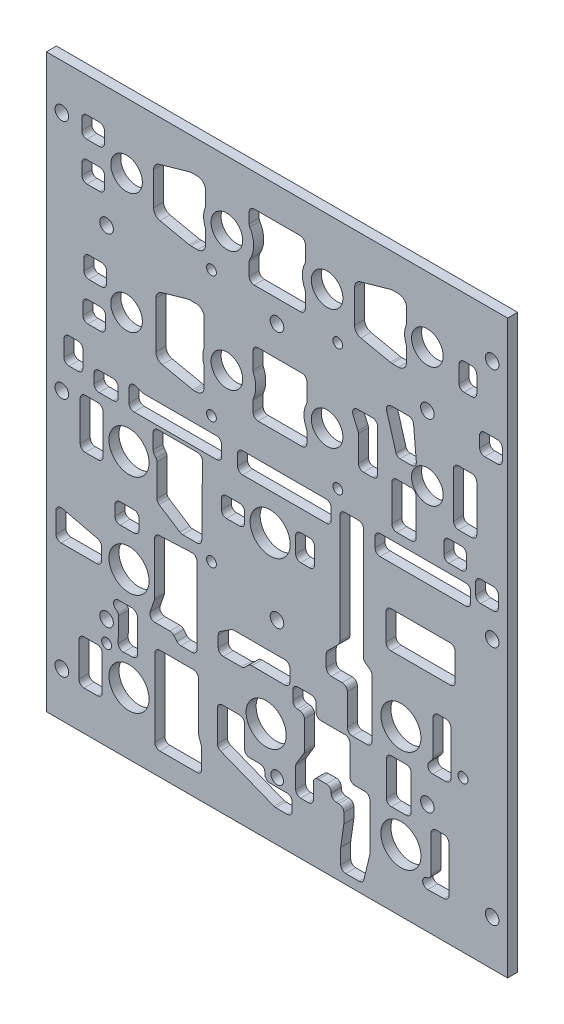
SolidWorks part; units mm, degrees
ref_plane "Front Plane" through (0, 0, 0) normal (0, 0, 1) x (1, 0, 0)
ref_plane "Top Plane" through (0, 0, 0) normal (0, 1, 0) x (1, 0, 0)
ref_plane "Right Plane" through (0, 0, 0) normal (1, 0, 0) x (0, 0, -1)
sketch "Sketch1" plane through (0, 0, 0) normal (0, 0, 1) x (1, 0, 0)
  line L4 (0, 180.975) -> (-146.05, 180.975)
  line L5 (-146.05, 180.975) -> (-146.05, 0)
  line L6 (-146.05, 0) -> (0, 0)
  line L7 (0, 0) -> (0, 180.975)
  line L8 (0, 180.975) -> (-146.05, 180.975)
  line L9 (-146.05, 180.975) -> (-146.05, 0)
  line L10 (-146.05, 0) -> (0, 0)
  line L11 (0, 0) -> (0, 180.975)
  dimension "D1" = 0
extrude "Boss-Extrude1" add sketch "Sketch1" against normal blind 3.175
hole_wizard "#6 Clearance Hole1" positions "Sketch3" profile "Sketch2" hole size "#6" standard "ANSI Inch" end condition through all
sketch "Sketch3" plane through (0, 0, -3.175) normal (0, 0, -1) x (-1, 0, 0)
  point P0 (25.4, 142.875)
  point P7 (73.025, 142.875)
  point P10 (127, 142.875)
  point P13 (25.4, 34.925)
  point P16 (73.025, 61.647)
  point P19 (127, 34.925)
  point P22 (4.8895, 14.2875)
  point P25 (141.1605, 14.2875)
  point P28 (4.8895, 90.4875)
  point P31 (141.1605, 90.4875)
  point P34 (141.1605, 166.6875)
  point P37 (4.8895, 166.6875)
sketch "Sketch2" plane through (-25.4, 142.875, -3.175) normal (1, 0, 0) x (0, 1, 0)
  line L0 (0, 0) -> (0, 3.175)
  line L1 (0, 3.175) -> (2.1526, 3.175)
  line L2 (2.1526, 3.175) -> (2.1526, 0)
  line L5 (2.1526, 0) -> (0, 0)
  line L11 (0, -6.35) -> (0, 107.95) construction
  dimension "Thru Hole Dia." = 4.3053
  dimension "Thru Hole Depth" = 3.175
hole_wizard "Ø10.0mm Dowel Hole1" positions "Sketch5" profile "Sketch4" hole size "Ø10.0" standard "ANSI Metric" end condition through all
sketch "Sketch5" plane through (0, 0, -3.175) normal (0, 0, -1) x (-1, 0, 0)
  point P0 (25.4, 160.3248)
  point P3 (57.15, 160.3248)
  point P6 (88.9, 160.3248)
  point P9 (120.65, 160.3248)
  point P12 (25.4, 122.2248)
  point P15 (57.15, 122.2248)
  point P18 (88.9, 122.2248)
  point P21 (120.65, 122.2248)
sketch "Sketch4" plane through (-25.4, 160.3248, -3.175) normal (1, 0, 0) x (0, 1, 0)
  line L0 (0, 0) -> (0, 3.175)
  line L1 (0, 3.175) -> (5, 3.175)
  line L2 (5, 3.175) -> (5, 0)
  line L5 (5, 0) -> (0, 0)
  line L11 (0, -6.35) -> (0, 107.95) construction
  dimension "Thru Hole Dia." = 10
  dimension "Thru Hole Depth" = 3.175
hole_wizard "1/2 (0.5) Diameter Hole1" positions "Sketch7" profile "Sketch6" hole size "1/2" standard "ANSI Inch" end condition through all
sketch "Sketch7" plane through (0, 0, -3.175) normal (0, 0, -1) x (-1, 0, 0)
  point P0 (75.184, 84.455)
  point P3 (119.888, 84.455)
  point P6 (119.888, 52.07)
  point P9 (33.782, 52.07)
  point P12 (33.782, 19.685)
  point P15 (119.888, 19.685)
  point P18 (76.454, 31.496)
sketch "Sketch6" plane through (-75.184, 84.455, -3.175) normal (1, 0, 0) x (0, 1, 0)
  line L0 (0, 0) -> (0, 3.175)
  line L1 (0, 3.175) -> (6.35, 3.175)
  line L2 (6.35, 3.175) -> (6.35, 0)
  line L5 (6.35, 0) -> (0, 0)
  line L11 (0, -6.35) -> (0, 107.95) construction
  dimension "Thru Hole Dia." = 12.7
  dimension "Thru Hole Depth" = 3.175
hole_wizard "5/32 (0.15625) Diameter Hole1" positions "Sketch9" profile "Sketch8" hole size "5/32" standard "ANSI Inch" end condition through all
sketch "Sketch9" plane through (0, 0, -3.175) normal (0, 0, -1) x (-1, 0, 0)
  point P0 (72.9632, 18.4682)
sketch "Sketch8" plane through (-72.9632, 18.4682, -3.175) normal (1, 0, 0) x (0, 1, 0)
  line L0 (0, 0) -> (0, 3.175)
  line L1 (0, 3.175) -> (1.9844, 3.175)
  line L2 (1.9844, 3.175) -> (1.9844, 0)
  line L5 (1.9844, 0) -> (0, 0)
  line L11 (0, -6.35) -> (0, 107.95) construction
  dimension "Thru Hole Dia." = 3.9688
  dimension "Thru Hole Depth" = 3.175
sketch "Sketch14" plane through (0, 0, -3.175) normal (0, 0, -1) x (-1, 0, 0)
  line L0 (9.7672, 160.6329) -> (9.7672, 155.3272)
  line L1 (11.3547, 153.7397) -> (13.8015, 153.7397)
  line L2 (15.389, 155.3272) -> (15.389, 160.6329)
  line L3 (13.8015, 162.2204) -> (11.3547, 162.2204)
  line L4 (34.5586, 170.4142) -> (36.4003, 170.4142)
  line L5 (37.0961, 170.317) -> (46.6191, 167.6046)
  line L6 (48.4633, 165.1617) -> (48.4633, 154.7406)
  line L7 (46.4489, 152.2556) -> (37.1235, 150.2836)
  line L8 (36.598, 150.2286) -> (34.5586, 150.2286)
  line L9 (32.0186, 152.7686) -> (32.0186, 156.9396)
  line L10 (32.0186, 163.6743) -> (32.0186, 167.8742)
  line L11 (98.2115, 170.808) -> (100.0532, 170.808)
  line L12 (100.749, 170.7109) -> (110.272, 167.9984)
  line L13 (112.1162, 165.5556) -> (112.1162, 155.1345)
  line L14 (110.1017, 152.6494) -> (100.7763, 150.6774)
  line L15 (100.2508, 150.6225) -> (98.2115, 150.6225)
  line L16 (95.6715, 153.1625) -> (95.6715, 157.3335)
  line L17 (95.6715, 164.0681) -> (95.6715, 168.268)
  line L18 (81.8281, 169.1678) -> (81.8281, 165.8804)
  line L19 (80.2406, 149.9091) -> (65.6522, 149.9091)
  line L20 (64.0647, 151.4966) -> (64.0647, 156.2088)
  line L21 (65.6522, 170.7553) -> (80.2406, 170.7553)
  line L22 (81.8281, 155.5212) -> (81.8281, 151.4966)
  line L23 (64.0647, 164.4051) -> (64.0647, 169.1678)
  line L24 (129.2512, 170.0673) -> (133.2539, 170.0673)
  line L25 (134.8414, 168.4798) -> (134.8414, 164.9772)
  line L26 (133.2539, 163.3897) -> (129.2512, 163.3897)
  line L27 (127.6637, 164.9772) -> (127.6637, 168.4798)
  line L28 (129.2048, 157.7974) -> (133.2075, 157.7974)
  line L29 (134.795, 156.2099) -> (134.795, 152.7072)
  line L30 (133.2075, 151.1197) -> (129.2048, 151.1197)
  line L31 (127.6173, 152.7072) -> (127.6173, 156.2099)
  line L38 (9.7672, 131.1028) -> (9.7672, 116.698)
  line L39 (3.2616, 146.0268) -> (7.2643, 146.0268)
  line L40 (8.8518, 144.4393) -> (8.8518, 140.9366)
  line L41 (7.2643, 139.3491) -> (3.2616, 139.3491)
  line L42 (1.6741, 140.9366) -> (1.6741, 144.4393)
  line L43 (31.3598, 138.4891) -> (36.773, 138.4891)
  line L44 (38.2969, 136.4568) -> (35.3321, 126.2979)
  line L45 (34.083, 125.3612) -> (30.4776, 125.3612)
  line L46 (28.8963, 127.0889) -> (29.7785, 137.0417)
  line L47 (11.3547, 115.1105) -> (15.5328, 115.1105)
  line L48 (17.1203, 116.698) -> (17.1203, 131.1028)
  line L49 (15.5328, 132.6903) -> (11.3547, 132.6903)
  line L50 (48.956, 130.0101) -> (47.363, 126.3421)
  line L51 (47.2316, 125.7097) -> (47.2316, 117.4914)
  line L52 (45.6441, 115.9039) -> (42.7293, 115.9039)
  line L53 (41.1418, 117.4914) -> (41.1418, 130.6425)
  line L54 (42.7293, 132.23) -> (47.4999, 132.23)
  line L55 (80.6037, 131.7198) -> (80.6037, 126.3538)
  line L56 (79.0162, 113.2168) -> (65.1559, 113.2168)
  line L57 (63.5684, 114.8043) -> (63.5684, 118.2429)
  line L58 (65.1559, 133.3073) -> (79.0162, 133.3073)
  line L59 (80.6037, 118.0601) -> (80.6037, 114.8043)
  line L60 (63.5684, 126.171) -> (63.5684, 131.7198)
  line L61 (98.5982, 135.6202) -> (100.6455, 135.6202)
  line L62 (101.3413, 135.523) -> (109.5302, 133.1906)
  line L63 (111.3744, 130.7477) -> (111.3744, 116.0074)
  line L64 (109.3599, 113.5224) -> (99.6649, 111.4722)
  line L65 (99.1394, 111.4172) -> (98.5982, 111.4172)
  line L66 (96.0582, 113.9572) -> (96.0582, 119.3928)
  line L67 (96.0582, 125.1954) -> (96.0582, 133.0802)
  line L68 (128.5836, 131.9356) -> (132.5863, 131.9356)
  line L69 (134.1738, 130.3481) -> (134.1738, 126.8454)
  line L70 (132.5863, 125.2579) -> (128.5836, 125.2579)
  line L71 (126.9961, 126.8454) -> (126.9961, 130.3481)
  line L72 (128.8955, 119.5754) -> (132.8982, 119.5754)
  line L73 (134.4857, 117.9879) -> (134.4857, 114.4852)
  line L74 (132.8982, 112.8977) -> (128.8955, 112.8977)
  line L75 (127.308, 114.4852) -> (127.308, 117.9879)
  line L80 (134.4857, 99.9647) -> (134.4857, 105.0965)
  line L81 (136.0732, 106.684) -> (138.8818, 106.684)
  line L82 (140.4693, 105.0965) -> (140.4693, 99.9647)
  line L83 (138.8818, 98.3772) -> (136.0732, 98.3772)
  line L84 (4.5173, 105.1016) -> (8.52, 105.1016)
  line L85 (10.1075, 103.5141) -> (10.1075, 100.0114)
  line L86 (8.52, 98.4239) -> (4.5173, 98.4239)
  line L87 (2.9298, 100.0114) -> (2.9298, 103.5141)
  line L88 (14.5909, 111.1372) -> (18.5937, 111.1372)
  line L89 (20.1812, 109.5497) -> (20.1812, 106.0471)
  line L90 (18.5937, 104.4596) -> (14.5909, 104.4596)
  line L91 (13.0034, 106.0471) -> (13.0034, 109.5497)
  line L92 (30.5353, 119.2048) -> (35.0928, 119.2048)
  line L93 (36.6803, 117.6173) -> (36.6803, 106.232)
  line L94 (35.0928, 104.6445) -> (30.5353, 104.6445)
  line L95 (28.9478, 106.232) -> (28.9478, 117.6173)
  line L96 (45.6441, 65.1535) -> (45.6441, 100.3349)
  line L97 (47.2316, 101.9224) -> (51.5303, 101.9224)
  line L98 (53.1178, 100.3349) -> (53.1178, 65.7835)
  line L100 (42.9626, 43.3689) -> (42.9626, 61.5953)
  line L101 (43.6218, 62.8831) -> (44.9849, 63.8657)
  line L102 (53.5828, 64.661) -> (56.969, 61.2747)
  line L103 (57.434, 60.1522) -> (57.434, 56.3979)
  line L104 (55.8465, 54.8104) -> (52.3434, 54.8104)
  line L105 (50.7559, 53.2229) -> (50.7559, 43.3689)
  line L106 (49.1684, 41.7814) -> (44.5501, 41.7814)
  line L107 (67.1117, 82.7287) -> (67.1117, 87.7639)
  line L108 (65.5242, 89.3514) -> (62.7089, 89.3514)
  line L109 (61.1214, 87.7639) -> (61.1214, 82.7287)
  line L110 (62.7089, 81.1412) -> (65.5242, 81.1412)
  line L111 (17.9628, 45.6888) -> (17.9628, 59.6872)
  line L112 (19.5503, 61.2747) -> (21.9934, 61.2747)
  line L113 (23.5809, 59.6872) -> (23.5809, 48.8911)
  line L114 (23.9452, 47.8792) -> (24.9202, 46.7007)
  line L115 (23.697, 44.1013) -> (19.5503, 44.1013)
  line L116 (25.4886, 14.7678) -> (25.6589, 14.7487)
  line L117 (24.2487, 16.3262) -> (24.2487, 27.6802)
  line L118 (22.6612, 29.2677) -> (20.1812, 29.2677)
  line L119 (18.5937, 27.6802) -> (18.5937, 13.2755)
  line L120 (20.1548, 11.6882) -> (25.2848, 11.603)
  line L121 (32.1228, 42.5427) -> (36.8165, 42.5427)
  line L122 (38.404, 40.9552) -> (38.404, 30.1729)
  line L123 (36.8165, 28.5854) -> (32.1228, 28.5854)
  line L124 (30.5353, 30.1729) -> (30.5353, 40.9552)
  line L131 (43.6218, 25.2523) -> (43.6218, 12.2392)
  line L132 (43.6651, 11.8711) -> (43.6953, 11.7446)
  line L133 (43.6953, 11.7446) -> (45.484, 4.241)
  line L134 (47.0282, 3.0216) -> (51.2631, 3.0216)
  line L135 (52.8506, 4.6091) -> (52.8506, 9.2853)
  line L136 (52.8343, 9.5123) -> (51.8747, 16.1533)
  line L137 (51.8584, 16.3803) -> (51.8584, 19.4808)
  line L138 (53.4459, 21.0683) -> (54.259, 21.0683)
  line L139 (55.8465, 22.6558) -> (55.8465, 22.9529)
  line L140 (57.434, 24.5404) -> (59.9239, 24.5404)
  line L142 (65.7683, 40.3849) -> (66.5835, 40.4562)
  line L143 (68.0326, 42.0377) -> (68.0326, 44.998)
  line L144 (66.4451, 46.5855) -> (62.2379, 46.5855)
  line L145 (60.6504, 44.998) -> (60.6504, 42.5992)
  line L146 (59.0629, 41.0117) -> (51.4951, 41.0117)
  line L147 (49.9076, 39.4242) -> (49.9076, 30.1729)
  line L148 (48.3201, 28.5854) -> (45.2093, 28.5854)
  line L149 (43.6218, 26.9979) -> (43.6218, 25.2523)
  line L150 (68.9553, 46.6546) -> (68.9553, 50.4494)
  line L151 (70.5428, 52.0369) -> (86.6326, 52.0369)
  line L152 (87.4873, 51.7871) -> (90.8944, 49.6101)
  line L153 (91.6271, 48.2724) -> (91.6271, 44.761)
  line L154 (90.0396, 43.1735) -> (84.3014, 43.1735)
  line L155 (83.1789, 43.6384) -> (82.1297, 44.6876)
  line L156 (80.9942, 45.1525) -> (70.5558, 45.0672)
  line L157 (67.1117, 24.5868) -> (67.1117, 18.1303)
  line L158 (65.5242, 16.5428) -> (63.0989, 16.5428)
  line L163 (61.5114, 18.1303) -> (61.5114, 22.9529)
  line L165 (66.8832, 25.4074) -> (64.5524, 29.2677)
  line L166 (64.3238, 30.0883) -> (64.3238, 38.9242)
  line L167 (91.9128, 18.299) -> (91.9128, 28.1134)
  line L168 (90.3253, 29.7009) -> (84.8895, 29.7009)
  line L169 (83.302, 28.1134) -> (83.302, 21.1236)
  line L170 (81.7145, 19.5361) -> (78.4438, 19.5361)
  line L171 (76.8563, 17.9486) -> (76.8563, 17.3807)
  line L172 (75.2688, 15.7932) -> (69.8184, 15.7932)
  line L173 (68.2309, 14.2057) -> (68.2309, 11.594)
  line L174 (69.8184, 10.0065) -> (73.3881, 10.0065)
  line L175 (73.9724, 10.1179) -> (90.9097, 16.8229)
  line L176 (84.8489, 87.7639) -> (89.0654, 87.7639)
  line L177 (90.6529, 86.1764) -> (90.6529, 83.1046)
  line L178 (89.0654, 81.5171) -> (84.8489, 81.5171)
  line L179 (83.2614, 83.1046) -> (83.2614, 86.1764)
  line L180 (129.7198, 92.9203) -> (133.7466, 92.9203)
  line L181 (135.3341, 91.3328) -> (135.3341, 78.857)
  line L182 (133.7466, 77.2695) -> (129.7198, 77.2695)
  line L183 (128.1323, 78.857) -> (128.1323, 91.3328)
  line L184 (143.02, 56.7173) -> (143.02, 50.184)
  line L185 (141.4325, 48.5965) -> (130.1711, 48.5965)
  line L186 (128.5836, 50.184) -> (128.5836, 54.036)
  line L187 (129.8034, 55.5803) -> (141.0648, 58.2616)
  line L188 (135.7336, 24.8954) -> (135.7336, 14.0589)
  line L189 (134.1461, 12.4714) -> (129.9507, 12.4714)
  line L190 (128.3632, 14.0589) -> (128.3632, 24.8954)
  line L191 (129.9507, 26.4829) -> (134.1461, 26.4829)
  line L192 (98.4374, 70.1232) -> (102.927, 70.1232)
  line L193 (103.7933, 70.3805) -> (110.3296, 74.6375)
  line L194 (111.0507, 75.9677) -> (111.0507, 86.0205)
  line L195 (111.3413, 86.936) -> (111.9636, 87.8177)
  line L196 (112.2542, 88.7332) -> (112.2542, 93.4348)
  line L197 (110.6667, 95.0223) -> (98.2147, 95.0223)
  line L198 (96.6273, 93.4186) -> (96.85, 71.6944)
  line L199 (13.2867, 101.7189) -> (40.3927, 101.7189)
  line L200 (41.9802, 100.1314) -> (41.9802, 96.9635)
  line L201 (40.3927, 95.376) -> (13.2867, 95.376)
  line L202 (11.6992, 96.9635) -> (11.6992, 100.1314)
  line L203 (83.9216, 102.6251) -> (57.434, 102.6251)
  line L204 (55.8465, 101.0376) -> (55.8465, 97.6017)
  line L205 (57.434, 96.0142) -> (83.9216, 96.0142)
  line L206 (85.5091, 97.6017) -> (85.5091, 101.0376)
  line L207 (92.1689, 102.6251) -> (115.232, 102.6251)
  line L208 (115.789, 102.726) -> (117.7111, 103.4462)
  line L209 (119.8556, 101.9596) -> (119.8556, 97.6777)
  line L210 (118.2681, 96.0902) -> (92.1689, 96.0902)
  line L211 (90.5814, 97.6777) -> (90.5814, 101.0376)
  line L212 (124.9027, 101.9596) -> (129.3791, 101.9596)
  line L213 (130.9666, 100.3721) -> (130.9666, 97.4731)
  line L214 (129.3791, 95.8856) -> (124.9027, 95.8856)
  line L215 (123.3152, 97.4731) -> (123.3152, 100.3721)
  line L216 (118.2868, 62.8831) -> (122.7428, 62.8831)
  line L217 (124.3303, 64.4706) -> (124.3303, 67.6675)
  line L218 (122.7428, 69.255) -> (118.2868, 69.255)
  line L219 (116.6993, 67.6675) -> (116.6993, 64.4706)
  line L220 (99.9975, 66.6672) -> (110.2768, 66.2149)
  line L221 (111.7946, 64.6289) -> (111.7946, 48.1514)
  line L222 (111.8816, 47.6331) -> (113.2086, 43.7913)
  line L223 (111.7081, 41.6855) -> (106.9185, 41.6855)
  line L224 (105.6937, 41.108) -> (104.7376, 39.9485)
  line L225 (103.5128, 39.371) -> (99.9277, 39.371)
  line L226 (98.3402, 40.9585) -> (98.3402, 65.0812)
  line L227 (123.3155, 30.1394) -> (123.1999, 37.6519)
  line L231 (117.1597, 40.098) -> (117.1597, 30.2424)
  line L232 (118.6794, 28.6564) -> (121.6604, 28.5289)
  line L235 (119.0974, 42.0356) -> (123.1757, 42.0356)
  line L236 (124.1569, 39.2002) -> (123.806, 38.9242)
  line L237 (18.1752, 71.248) -> (36.9199, 71.248)
  line L238 (99.477, 34.8237) -> (110.1206, 34.8237)
  line L239 (111.7081, 33.2362) -> (111.7081, 8.7739)
  line L240 (110.1206, 7.1864) -> (98.4375, 7.1864)
  line L241 (96.85, 8.7739) -> (96.85, 14.4973)
  line L242 (96.9277, 14.9877) -> (97.8118, 17.7095)
  line L243 (97.8895, 18.1999) -> (97.8895, 33.2362)
  line L244 (38.5074, 72.8355) -> (38.5074, 81.2425)
  line L245 (36.9199, 82.83) -> (18.1752, 82.83)
  line L246 (16.5877, 81.2425) -> (16.5877, 72.8355)
  line L247 (93.7721, 147.2947) -> (53.7721, 147.2947) construction
  line L248 (93.7721, 147.2947) -> (93.7721, 107.2947) construction
  line L249 (93.7721, 107.2947) -> (53.7721, 107.2947) construction
  line L250 (53.7721, 147.2947) -> (53.7721, 107.2947) construction
  line L251 (93.7721, 107.2947) -> (93.7721, 67.2947) construction
  arc A0 (13.8015, 153.7397) -> (15.389, 155.3272) centre (13.8015, 155.3272) ccw
  arc A1 (9.7672, 160.6329) -> (11.3547, 162.2204) centre (11.3547, 160.6329) cw
  arc A2 (15.389, 160.6329) -> (13.8015, 162.2204) centre (13.8015, 160.6329) ccw
  arc A3 (9.7672, 155.3272) -> (11.3547, 153.7397) centre (11.3547, 155.3272) ccw
  arc A4 (34.5586, 150.2286) -> (32.0186, 152.7686) centre (34.5586, 152.7686) cw
  arc A5 (37.1235, 150.2836) -> (36.598, 150.2286) centre (36.598, 152.7686) cw
  arc A6 (48.4633, 154.7406) -> (46.4489, 152.2556) centre (45.9233, 154.7406) cw
  arc A7 (46.6191, 167.6046) -> (48.4633, 165.1617) centre (45.9233, 165.1617) cw
  arc A8 (36.4003, 170.4142) -> (37.0961, 170.317) centre (36.4003, 167.8742) cw
  arc A9 (34.5586, 170.4142) -> (32.0186, 167.8742) centre (34.5586, 167.8742) ccw
  arc A10 (32.1741, 157.8147) -> (32.1741, 162.7992) centre (25.3826, 160.3069) ccw
  arc A11 (32.1741, 162.7992) -> (32.0186, 163.6743) centre (34.5586, 163.6743) cw
  arc A12 (32.1741, 157.8147) -> (32.0186, 156.9396) centre (34.5586, 156.9396) ccw
  arc A13 (98.2115, 150.6225) -> (95.6715, 153.1625) centre (98.2115, 153.1625) cw
  arc A14 (100.7763, 150.6774) -> (100.2508, 150.6225) centre (100.2508, 153.1625) cw
  arc A15 (112.1162, 155.1345) -> (110.1017, 152.6494) centre (109.5762, 155.1345) cw
  arc A16 (110.272, 167.9984) -> (112.1162, 165.5556) centre (109.5762, 165.5556) cw
  arc A17 (100.0532, 170.808) -> (100.749, 170.7109) centre (100.0532, 168.268) cw
  arc A18 (98.2115, 170.808) -> (95.6715, 168.268) centre (98.2115, 168.268) ccw
  arc A19 (95.8269, 158.2085) -> (95.8269, 163.1931) centre (89.0355, 160.7008) ccw
  arc A20 (95.8269, 163.1931) -> (95.6715, 164.0681) centre (98.2115, 164.0681) cw
  arc A21 (95.8269, 158.2085) -> (95.6715, 157.3335) centre (98.2115, 157.3335) ccw
  arc A22 (64.2216, 156.8969) -> (64.2216, 163.7169) centre (57.1326, 160.3069) ccw
  arc A23 (81.6085, 165.0748) -> (81.6085, 156.3268) centre (89.0355, 160.7008) ccw
  arc A24 (64.2216, 163.7169) -> (64.0647, 164.4051) centre (65.6522, 164.4051) cw
  arc A25 (64.2216, 156.8969) -> (64.0647, 156.2088) centre (65.6522, 156.2088) ccw
  arc A26 (81.6085, 156.3268) -> (81.8281, 155.5212) centre (80.2406, 155.5212) cw
  arc A27 (81.6085, 165.0748) -> (81.8281, 165.8804) centre (80.2406, 165.8804) ccw
  arc A28 (81.8281, 169.1678) -> (80.2406, 170.7553) centre (80.2406, 169.1678) ccw
  arc A29 (64.0647, 169.1678) -> (65.6522, 170.7553) centre (65.6522, 169.1678) cw
  arc A30 (65.6522, 149.9091) -> (64.0647, 151.4966) centre (65.6522, 151.4966) cw
  arc A31 (81.8281, 151.4966) -> (80.2406, 149.9091) centre (80.2406, 151.4966) cw
  arc A32 (129.2512, 170.0673) -> (127.6637, 168.4798) centre (129.2512, 168.4798) ccw
  arc A33 (129.2512, 163.3897) -> (127.6637, 164.9772) centre (129.2512, 164.9772) cw
  arc A34 (134.8414, 164.9772) -> (133.2539, 163.3897) centre (133.2539, 164.9772) cw
  arc A35 (133.2539, 170.0673) -> (134.8414, 168.4798) centre (133.2539, 168.4798) cw
  arc A36 (129.2048, 157.7974) -> (127.6173, 156.2099) centre (129.2048, 156.2099) ccw
  arc A37 (129.2048, 151.1197) -> (127.6173, 152.7072) centre (129.2048, 152.7072) cw
  arc A38 (134.795, 152.7072) -> (133.2075, 151.1197) centre (133.2075, 152.7072) cw
  arc A39 (133.2075, 157.7974) -> (134.795, 156.2099) centre (133.2075, 156.2099) cw
  arc A50 (29.7785, 137.0417) -> (31.3598, 138.4891) centre (31.3598, 136.9016) cw
  arc A51 (3.2616, 146.0268) -> (1.6741, 144.4393) centre (3.2616, 144.4393) ccw
  arc A52 (3.2616, 139.3491) -> (1.6741, 140.9366) centre (3.2616, 140.9366) cw
  arc A53 (8.8518, 140.9366) -> (7.2643, 139.3491) centre (7.2643, 140.9366) cw
  arc A54 (7.2643, 146.0268) -> (8.8518, 144.4393) centre (7.2643, 144.4393) cw
  arc A55 (128.5836, 131.9356) -> (126.9961, 130.3481) centre (128.5836, 130.3481) ccw
  arc A56 (36.773, 138.4891) -> (38.2969, 136.4568) centre (36.773, 136.9016) cw
  arc A57 (30.4776, 125.3612) -> (28.8963, 127.0889) centre (30.4776, 126.9487) cw
  arc A58 (35.3321, 126.2979) -> (34.083, 125.3612) centre (34.083, 126.6624) cw
  arc A60 (9.7672, 116.698) -> (11.3547, 115.1105) centre (11.3547, 116.698) ccw
  arc A61 (15.5328, 115.1105) -> (17.1203, 116.698) centre (15.5328, 116.698) ccw
  arc A62 (17.1203, 131.1028) -> (15.5328, 132.6903) centre (15.5328, 131.1028) ccw
  arc A63 (9.7672, 131.1028) -> (11.3547, 132.6903) centre (11.3547, 131.1028) cw
  arc A64 (42.7293, 115.9039) -> (41.1418, 117.4914) centre (42.7293, 117.4914) cw
  arc A65 (47.2316, 117.4914) -> (45.6441, 115.9039) centre (45.6441, 117.4914) cw
  arc A66 (47.363, 126.3421) -> (47.2316, 125.7097) centre (48.8191, 125.7097) ccw
  arc A67 (41.1418, 130.6425) -> (42.7293, 132.23) centre (42.7293, 130.6425) cw
  arc A68 (48.956, 130.0101) -> (47.4999, 132.23) centre (47.4999, 130.6425) ccw
  arc A69 (80.4797, 125.7387) -> (80.4797, 118.6752) centre (88.8826, 122.2069) ccw
  arc A70 (63.7326, 118.9461) -> (63.7326, 125.4678) centre (57.1326, 122.2069) ccw
  arc A71 (63.7326, 125.4678) -> (63.5684, 126.171) centre (65.1559, 126.171) cw
  arc A72 (63.7326, 118.9461) -> (63.5684, 118.2429) centre (65.1559, 118.2429) ccw
  arc A73 (65.1559, 113.2168) -> (63.5684, 114.8043) centre (65.1559, 114.8043) cw
  arc A74 (80.6037, 114.8043) -> (79.0162, 113.2168) centre (79.0162, 114.8043) cw
  arc A75 (80.4797, 118.6752) -> (80.6037, 118.0601) centre (79.0162, 118.0601) cw
  arc A76 (80.4797, 125.7387) -> (80.6037, 126.3538) centre (79.0162, 126.3538) ccw
  arc A77 (80.6037, 131.7198) -> (79.0162, 133.3073) centre (79.0162, 131.7198) ccw
  arc A78 (63.5684, 131.7198) -> (65.1559, 133.3073) centre (65.1559, 131.7198) cw
  arc A79 (98.5982, 111.4172) -> (96.0582, 113.9572) centre (98.5982, 113.9572) cw
  arc A80 (99.6649, 111.4722) -> (99.1394, 111.4172) centre (99.1394, 113.9572) cw
  arc A81 (111.3744, 116.0074) -> (109.3599, 113.5224) centre (108.8344, 116.0074) cw
  arc A82 (109.5302, 133.1906) -> (111.3744, 130.7477) centre (108.8344, 130.7477) cw
  arc A83 (100.6455, 135.6202) -> (101.3413, 135.523) centre (100.6455, 133.0802) cw
  arc A84 (98.5982, 135.6202) -> (96.0582, 133.0802) centre (98.5982, 133.0802) ccw
  arc A85 (96.1501, 119.9657) -> (96.1501, 124.6224) centre (89.0819, 122.2941) ccw
  arc A86 (96.1501, 124.6224) -> (96.0582, 125.1954) centre (97.8895, 125.1954) cw
  arc A87 (96.1501, 119.9657) -> (96.0582, 119.3928) centre (97.8895, 119.3928) ccw
  arc A88 (128.5836, 125.2579) -> (126.9961, 126.8454) centre (128.5836, 126.8454) cw
  arc A89 (134.1738, 126.8454) -> (132.5863, 125.2579) centre (132.5863, 126.8454) cw
  arc A90 (132.5863, 131.9356) -> (134.1738, 130.3481) centre (132.5863, 130.3481) cw
  arc A91 (128.8955, 119.5754) -> (127.308, 117.9879) centre (128.8955, 117.9879) ccw
  arc A92 (128.8955, 112.8977) -> (127.308, 114.4852) centre (128.8955, 114.4852) cw
  arc A93 (134.4857, 114.4852) -> (132.8982, 112.8977) centre (132.8982, 114.4852) cw
  arc A94 (132.8982, 119.5754) -> (134.4857, 117.9879) centre (132.8982, 117.9879) cw
  arc A99 (134.4857, 99.9647) -> (136.0732, 98.3772) centre (136.0732, 99.9647) ccw
  arc A100 (140.4693, 99.9647) -> (138.8818, 98.3772) centre (138.8818, 99.9647) cw
  arc A101 (138.8818, 106.684) -> (140.4693, 105.0965) centre (138.8818, 105.0965) cw
  arc A102 (134.4857, 105.0965) -> (136.0732, 106.684) centre (136.0732, 105.0965) cw
  arc A103 (4.5173, 105.1016) -> (2.9298, 103.5141) centre (4.5173, 103.5141) ccw
  arc A104 (4.5173, 98.4239) -> (2.9298, 100.0114) centre (4.5173, 100.0114) cw
  arc A105 (10.1075, 100.0114) -> (8.52, 98.4239) centre (8.52, 100.0114) cw
  arc A106 (8.52, 105.1016) -> (10.1075, 103.5141) centre (8.52, 103.5141) cw
  arc A107 (14.5909, 111.1372) -> (13.0034, 109.5497) centre (14.5909, 109.5497) ccw
  arc A108 (14.5909, 104.4596) -> (13.0034, 106.0471) centre (14.5909, 106.0471) cw
  arc A109 (20.1812, 106.0471) -> (18.5937, 104.4596) centre (18.5937, 106.0471) cw
  arc A110 (18.5937, 111.1372) -> (20.1812, 109.5497) centre (18.5937, 109.5497) cw
  arc A111 (30.5353, 119.2048) -> (28.9478, 117.6173) centre (30.5353, 117.6173) ccw
  arc A112 (30.5353, 104.6445) -> (28.9478, 106.232) centre (30.5353, 106.232) cw
  arc A113 (36.6803, 106.232) -> (35.0928, 104.6445) centre (35.0928, 106.232) cw
  arc A114 (35.0928, 119.2048) -> (36.6803, 117.6173) centre (35.0928, 117.6173) cw
  arc A115 (45.6441, 100.3349) -> (47.2316, 101.9224) centre (47.2316, 100.3349) cw
  arc A116 (51.5303, 101.9224) -> (53.1178, 100.3349) centre (51.5303, 100.3349) cw
  arc A119 (53.1178, 65.7835) -> (53.5828, 64.661) centre (54.7053, 65.7835) ccw
  arc A120 (56.969, 61.2747) -> (57.434, 60.1522) centre (55.8465, 60.1522) cw
  arc A121 (57.434, 56.3979) -> (55.8465, 54.8104) centre (55.8465, 56.3979) cw
  arc A122 (42.9626, 43.3689) -> (44.5501, 41.7814) centre (44.5501, 43.3689) ccw
  arc A123 (50.7559, 43.3689) -> (49.1684, 41.7814) centre (49.1684, 43.3689) cw
  arc A124 (52.3434, 54.8104) -> (50.7559, 53.2229) centre (52.3434, 53.2229) ccw
  arc A125 (42.9626, 61.5953) -> (43.6218, 62.8831) centre (44.5501, 61.5953) cw
  arc A126 (45.6441, 65.1535) -> (44.9849, 63.8657) centre (44.0566, 65.1535) cw
  arc A127 (61.1214, 82.7287) -> (62.7089, 81.1412) centre (62.7089, 82.7287) ccw
  arc A128 (62.7089, 89.3514) -> (61.1214, 87.7639) centre (62.7089, 87.7639) ccw
  arc A129 (67.1117, 87.7639) -> (65.5242, 89.3514) centre (65.5242, 87.7639) ccw
  arc A130 (67.1117, 82.7287) -> (65.5242, 81.1412) centre (65.5242, 82.7287) cw
  arc A131 (17.9628, 59.6872) -> (19.5503, 61.2747) centre (19.5503, 59.6872) cw
  arc A132 (21.9934, 61.2747) -> (23.5809, 59.6872) centre (21.9934, 59.6872) cw
  arc A133 (23.5809, 48.8911) -> (23.9452, 47.8792) centre (25.1684, 48.8911) ccw
  arc A134 (24.9202, 46.7007) -> (23.697, 44.1013) centre (23.697, 45.6888) cw
  arc A135 (17.9628, 45.6888) -> (19.5503, 44.1013) centre (19.5503, 45.6888) ccw
  circle A136 centre (14.1329, 47.8792) radius 1.5875
  arc A137 (20.1812, 29.2677) -> (18.5937, 27.6802) centre (20.1812, 27.6802) ccw
  arc A138 (24.2487, 27.6802) -> (22.6612, 29.2677) centre (22.6612, 27.6802) ccw
  arc A139 (18.5937, 13.2755) -> (20.1548, 11.6882) centre (20.1812, 13.2755) ccw
  arc A140 (25.4886, 14.7678) -> (25.2848, 11.603) centre (25.3112, 13.1902) cw
  arc A141 (25.6589, 14.7487) -> (24.2487, 16.3262) centre (25.8362, 16.3262) cw
  arc A142 (32.1228, 42.5427) -> (30.5353, 40.9552) centre (32.1228, 40.9552) ccw
  arc A143 (36.8165, 42.5427) -> (38.404, 40.9552) centre (36.8165, 40.9552) cw
  arc A144 (38.404, 30.1729) -> (36.8165, 28.5854) centre (36.8165, 30.1729) cw
  arc A145 (32.1228, 28.5854) -> (30.5353, 30.1729) centre (32.1228, 30.1729) cw
  arc A151 (43.6218, 12.2392) -> (43.6651, 11.8711) centre (45.2093, 12.2392) ccw
  arc A152 (45.2093, 28.5854) -> (43.6218, 26.9979) centre (45.2093, 26.9979) ccw
  arc A153 (49.9076, 30.1729) -> (48.3201, 28.5854) centre (48.3201, 30.1729) cw
  arc A154 (51.4951, 41.0117) -> (49.9076, 39.4242) centre (51.4951, 39.4242) ccw
  arc A155 (60.6504, 42.5992) -> (59.0629, 41.0117) centre (59.0629, 42.5992) cw
  arc A156 (62.2379, 46.5855) -> (60.6504, 44.998) centre (62.2379, 44.998) ccw
  arc A157 (68.0326, 44.998) -> (66.4451, 46.5855) centre (66.4451, 44.998) ccw
  arc A158 (66.5835, 40.4562) -> (68.0326, 42.0377) centre (66.4451, 42.0377) ccw
  arc A159 (64.3238, 38.9242) -> (65.7683, 40.3849) centre (65.9067, 38.8034) cw
  arc A161 (55.8465, 22.9529) -> (57.434, 24.5404) centre (57.434, 22.9529) cw
  arc A162 (51.8584, 19.4808) -> (53.4459, 21.0683) centre (53.4459, 19.4808) cw
  arc A163 (51.8747, 16.1533) -> (51.8584, 16.3803) centre (53.4459, 16.3803) cw
  arc A164 (52.8506, 9.2853) -> (52.8343, 9.5123) centre (51.2631, 9.2853) ccw
  arc A165 (51.2631, 3.0216) -> (52.8506, 4.6091) centre (51.2631, 4.6091) ccw
  arc A166 (45.484, 4.241) -> (47.0282, 3.0216) centre (47.0282, 4.6091) ccw
  arc A167 (54.259, 21.0683) -> (55.8465, 22.6558) centre (54.259, 22.6558) ccw
  arc A168 (82.1297, 44.6876) -> (80.9942, 45.1525) centre (81.0072, 43.5651) ccw
  arc A169 (84.3014, 43.1735) -> (83.1789, 43.6384) centre (84.3014, 44.761) cw
  arc A170 (91.6271, 44.761) -> (90.0396, 43.1735) centre (90.0396, 44.761) cw
  arc A171 (90.8944, 49.6101) -> (91.6271, 48.2724) centre (90.0396, 48.2724) cw
  arc A172 (86.6326, 52.0369) -> (87.4873, 51.7871) centre (86.6326, 50.4494) cw
  arc A173 (68.9553, 50.4494) -> (70.5428, 52.0369) centre (70.5428, 50.4494) cw
  arc A174 (68.9553, 46.6546) -> (70.5558, 45.0672) centre (70.5428, 46.6546) ccw
  arc A175 (67.1117, 18.1303) -> (65.5242, 16.5428) centre (65.5242, 18.1303) cw
  arc A176 (63.0989, 16.5428) -> (61.5114, 18.1303) centre (63.0989, 18.1303) cw
  arc A177 (61.5114, 22.9529) -> (59.9239, 24.5404) centre (59.9239, 22.9529) ccw
  arc A178 (67.1117, 24.5868) -> (66.8832, 25.4074) centre (65.5242, 24.5868) ccw
  arc A179 (64.5524, 29.2677) -> (64.3238, 30.0883) centre (65.9113, 30.0883) cw
  arc A180 (91.9128, 18.299) -> (90.9097, 16.8229) centre (90.3253, 18.299) cw
  arc A181 (91.9128, 28.1134) -> (90.3253, 29.7009) centre (90.3253, 28.1134) ccw
  arc A182 (84.8895, 29.7009) -> (83.302, 28.1134) centre (84.8895, 28.1134) ccw
  arc A183 (83.302, 21.1236) -> (81.7145, 19.5361) centre (81.7145, 21.1236) cw
  arc A184 (78.4438, 19.5361) -> (76.8563, 17.9486) centre (78.4438, 17.9486) ccw
  arc A185 (76.8563, 17.3807) -> (75.2688, 15.7932) centre (75.2688, 17.3807) cw
  arc A186 (69.8184, 15.7932) -> (68.2309, 14.2057) centre (69.8184, 14.2057) ccw
  arc A187 (68.2309, 11.594) -> (69.8184, 10.0065) centre (69.8184, 11.594) ccw
  arc A188 (73.3881, 10.0065) -> (73.9724, 10.1179) centre (73.3881, 11.594) ccw
  arc A189 (89.0654, 87.7639) -> (90.6529, 86.1764) centre (89.0654, 86.1764) cw
  arc A190 (90.6529, 83.1046) -> (89.0654, 81.5171) centre (89.0654, 83.1046) cw
  arc A191 (84.8489, 81.5171) -> (83.2614, 83.1046) centre (84.8489, 83.1046) cw
  arc A192 (84.8489, 87.7639) -> (83.2614, 86.1764) centre (84.8489, 86.1764) ccw
  arc A193 (129.7198, 77.2695) -> (128.1323, 78.857) centre (129.7198, 78.857) cw
  arc A194 (135.3341, 78.857) -> (133.7466, 77.2695) centre (133.7466, 78.857) cw
  arc A195 (133.7466, 92.9203) -> (135.3341, 91.3328) centre (133.7466, 91.3328) cw
  arc A196 (129.7198, 92.9203) -> (128.1323, 91.3328) centre (129.7198, 91.3328) ccw
  arc A197 (128.5836, 54.036) -> (129.8034, 55.5803) centre (130.1711, 54.036) cw
  arc A198 (130.1711, 48.5965) -> (128.5836, 50.184) centre (130.1711, 50.184) cw
  arc A199 (143.02, 50.184) -> (141.4325, 48.5965) centre (141.4325, 50.184) cw
  arc A200 (143.02, 56.7173) -> (141.0648, 58.2616) centre (141.4325, 56.7173) ccw
  arc A201 (129.9507, 12.4714) -> (128.3632, 14.0589) centre (129.9507, 14.0589) cw
  arc A202 (135.7336, 14.0589) -> (134.1461, 12.4714) centre (134.1461, 14.0589) cw
  arc A203 (128.3632, 24.8954) -> (129.9507, 26.4829) centre (129.9507, 24.8954) cw
  arc A204 (135.7336, 24.8954) -> (134.1461, 26.4829) centre (134.1461, 24.8954) ccw
  arc A205 (98.2147, 95.0223) -> (96.6273, 93.4186) centre (98.2147, 93.4348) ccw
  arc A206 (112.2542, 93.4348) -> (110.6667, 95.0223) centre (110.6667, 93.4348) ccw
  arc A207 (111.9636, 87.8177) -> (112.2542, 88.7332) centre (110.6667, 88.7332) ccw
  arc A208 (111.0507, 86.0205) -> (111.3413, 86.936) centre (112.6382, 86.0205) cw
  arc A209 (110.3296, 74.6375) -> (111.0507, 75.9677) centre (109.4632, 75.9677) ccw
  arc A210 (102.927, 70.1232) -> (103.7933, 70.3805) centre (102.927, 71.7107) ccw
  arc A211 (98.4374, 70.1232) -> (96.85, 71.6944) centre (98.4374, 71.7107) cw
  arc A212 (40.3927, 101.7189) -> (41.9802, 100.1314) centre (40.3927, 100.1314) cw
  arc A213 (41.9802, 96.9635) -> (40.3927, 95.376) centre (40.3927, 96.9635) cw
  arc A214 (13.2867, 95.376) -> (11.6992, 96.9635) centre (13.2867, 96.9635) cw
  arc A215 (13.2867, 101.7189) -> (11.6992, 100.1314) centre (13.2867, 100.1314) ccw
  arc A216 (83.9216, 102.6251) -> (85.5091, 101.0376) centre (83.9216, 101.0376) cw
  arc A217 (83.9216, 96.0142) -> (85.5091, 97.6017) centre (83.9216, 97.6017) ccw
  arc A218 (55.8465, 97.6017) -> (57.434, 96.0142) centre (57.434, 97.6017) ccw
  arc A219 (57.434, 102.6251) -> (55.8465, 101.0376) centre (57.434, 101.0376) ccw
  arc A220 (115.232, 102.6251) -> (115.789, 102.726) centre (115.232, 104.2126) ccw
  arc A221 (117.7111, 103.4462) -> (119.8556, 101.9596) centre (118.2681, 101.9596) cw
  arc A222 (119.8556, 97.6777) -> (118.2681, 96.0902) centre (118.2681, 97.6777) cw
  arc A223 (92.1689, 96.0902) -> (90.5814, 97.6777) centre (92.1689, 97.6777) cw
  arc A224 (92.1689, 102.6251) -> (90.5814, 101.0376) centre (92.1689, 101.0376) ccw
  arc A225 (129.3791, 101.9596) -> (130.9666, 100.3721) centre (129.3791, 100.3721) cw
  arc A226 (130.9666, 97.4731) -> (129.3791, 95.8856) centre (129.3791, 97.4731) cw
  arc A227 (124.9027, 95.8856) -> (123.3152, 97.4731) centre (124.9027, 97.4731) cw
  arc A228 (124.9027, 101.9596) -> (123.3152, 100.3721) centre (124.9027, 100.3721) ccw
  arc A229 (118.2868, 69.255) -> (116.6993, 67.6675) centre (118.2868, 67.6675) ccw
  arc A230 (118.2868, 62.8831) -> (116.6993, 64.4706) centre (118.2868, 64.4706) cw
  arc A231 (122.7428, 62.8831) -> (124.3303, 64.4706) centre (122.7428, 64.4706) ccw
  arc A232 (124.3303, 67.6675) -> (122.7428, 69.255) centre (122.7428, 67.6675) ccw
  arc A233 (99.9277, 39.371) -> (98.3402, 40.9585) centre (99.9277, 40.9585) cw
  arc A234 (104.7376, 39.9485) -> (103.5128, 39.371) centre (103.5128, 40.9585) cw
  arc A235 (106.9185, 41.6855) -> (105.6937, 41.108) centre (106.9185, 40.098) ccw
  arc A236 (113.2086, 43.7913) -> (111.7081, 41.6855) centre (111.7081, 43.273) cw
  arc A237 (111.7946, 48.1514) -> (111.8816, 47.6331) centre (113.3821, 48.1514) ccw
  arc A238 (110.2768, 66.2149) -> (111.7946, 64.6289) centre (110.2071, 64.6289) cw
  arc A239 (99.9975, 66.6672) -> (98.3402, 65.0812) centre (99.9277, 65.0812) ccw
  arc A240 (123.3155, 30.1394) -> (121.6604, 28.5289) centre (121.7282, 30.1149) cw
  arc A241 (117.1597, 30.2424) -> (118.6794, 28.6564) centre (118.7472, 30.2424) ccw
  arc A243 (119.0974, 42.0356) -> (117.1597, 40.098) centre (119.0974, 40.098) ccw
  arc A246 (123.1999, 37.6519) -> (123.806, 38.9242) centre (124.7872, 37.6763) cw
  arc A247 (123.1757, 42.0356) -> (124.1569, 39.2002) centre (123.1757, 40.4481) cw
  circle A248 centre (126.963, 28.3176) radius 1.5875
  arc A249 (97.8118, 17.7095) -> (97.8895, 18.1999) centre (96.302, 18.1999) ccw
  arc A250 (96.85, 14.4973) -> (96.9277, 14.9877) centre (98.4375, 14.4973) cw
  arc A251 (98.4375, 7.1864) -> (96.85, 8.7739) centre (98.4375, 8.7739) cw
  arc A252 (111.7081, 8.7739) -> (110.1206, 7.1864) centre (110.1206, 8.7739) cw
  arc A253 (110.1206, 34.8237) -> (111.7081, 33.2362) centre (110.1206, 33.2362) cw
  arc A254 (99.477, 34.8237) -> (97.8895, 33.2362) centre (99.477, 33.2362) ccw
  arc A255 (36.9199, 71.248) -> (38.5074, 72.8355) centre (36.9199, 72.8355) ccw
  arc A256 (38.5074, 81.2425) -> (36.9199, 82.83) centre (36.9199, 81.2425) ccw
  arc A257 (18.1752, 82.83) -> (16.5877, 81.2425) centre (18.1752, 81.2425) ccw
  arc A258 (18.1752, 71.248) -> (16.5877, 72.8355) centre (18.1752, 72.8355) cw
  circle A259 centre (53.7721, 147.2947) radius 1.55
  circle A260 centre (93.7721, 147.2947) radius 1.55
  circle A261 centre (53.7721, 107.2947) radius 1.55
  circle A262 centre (93.7721, 107.2947) radius 1.55
  circle A263 centre (93.7721, 67.2947) radius 1.55
  point P36 (32.0186, 163.1878)
  point P76 (64.0647, 164.0256)
  point P81 (81.8281, 155.9737)
  point P145 (28.7432, 125.3612)
  point P182 (63.5684, 125.781)
  point P191 (80.6037, 118.3935)
  dimension "D1" = 1.5875
  dimension "D2" = 2.54
  dimension "D3" = 2.54
  dimension "D4" = 1.5875
  dimension "D5" = 1.5875
  dimension "D6" = 1.5875
  dimension "D7" = 1.5875
  dimension "D8" = 1.5875
  dimension "D9" = 1.5875
  dimension "D10" = 1.5875
  dimension "D11" = 1.5875
  dimension "D12" = 1.5875
  dimension "D13" = 1.5875
  dimension "D14" = 1.5875
  dimension "D15" = 1.5875
  dimension "D16" = 1.5875
  dimension "D17" = 1.5875
  dimension "D18" = 1.5875
  dimension "D19" = 1.5875
  dimension "D20" = 1.5875
  dimension "D21" = 1.5875
  dimension "D22" = 1.5875
  dimension "D23" = 3.175
  dimension "D24" = 1.5875
  dimension "D25" = 1.5875
  dimension "D26" = 1.5875
  dimension "D27" = 1.5875
  dimension "D28" = 1.5875
  dimension "D29" = 1.5875
  dimension "D30" = 1.5875
  dimension "D31" = 1.5875
  dimension "D32" = 1.5875
  dimension "D33" = 1.5875
  dimension "D34" = 1.5875
  dimension "D35" = 1.5875
  dimension "D36" = 1.5875
  dimension "D37" = 1.5875
  dimension "D38" = 1.5875
  dimension "D39" = 1.5875
  dimension "D40" = 1.5875
  dimension "D41" = 1.5875
  dimension "D42" = 1.5875
  dimension "D43" = 1.5875
  dimension "D44" = 1.5875
  dimension "D45" = 1.5875
  dimension "D46" = 3.175
  dimension "D47" = 1.5875
  dimension "D48" = 1.5875
  dimension "D49" = 3.1
  dimension "D50" = 3.1
  dimension "D51" = 3.1
  dimension "D52" = 3.1
  dimension "D55" = 3.1
  dimension "D53" = 40
  dimension "D54" = 40
  dimension "D56" = 40
extrude "Cut-Extrude1" cut sketch "Sketch14" against normal through all
